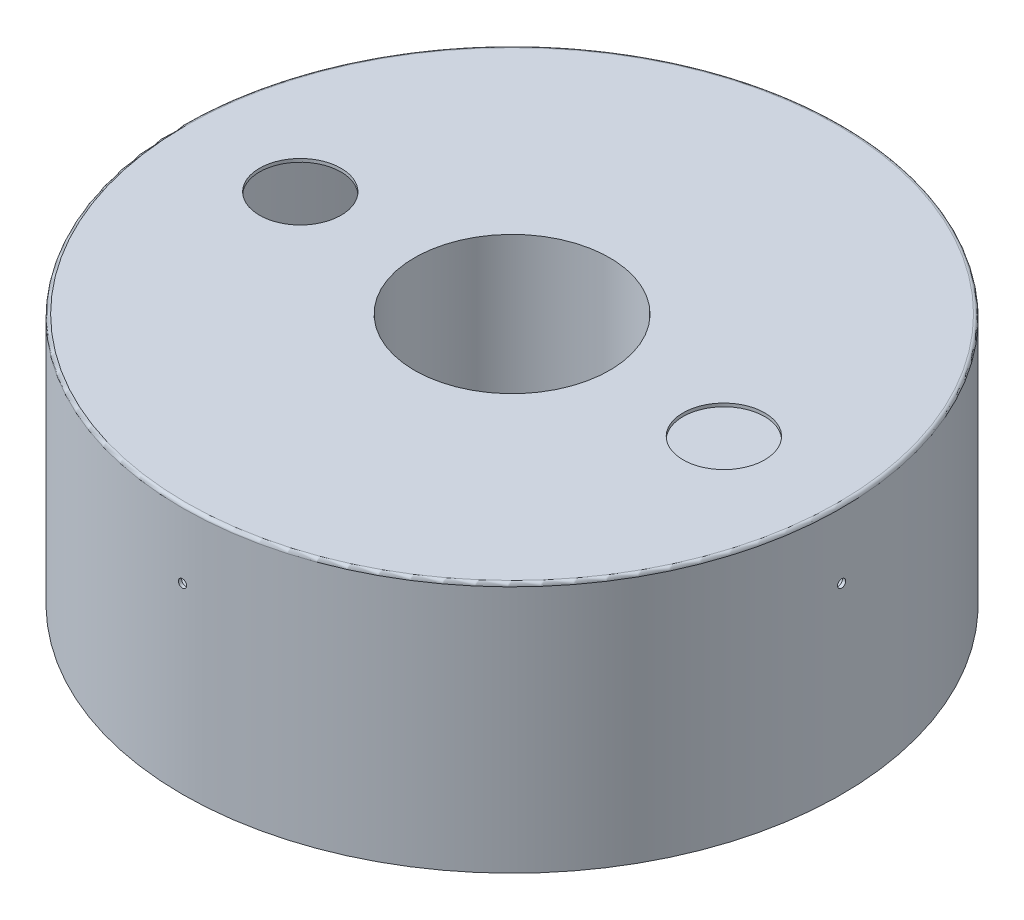
SolidWorks part; units mm, degrees
material "2014 Alloy"
ref_plane "Front Plane" through (0, 0, 0) normal (0, 0, 1) x (1, 0, 0)
ref_plane "Top Plane" through (0, 0, 0) normal (0, 1, 0) x (1, 0, 0)
ref_plane "Right Plane" through (0, 0, 0) normal (1, 0, 0) x (0, 0, -1)
sketch "Sketch9" plane through (0, 0, 0) normal (0, 1, 0) x (1, 0, 0)
  circle A0 centre (0, 0) radius 2000
extrude "Boss-Extrude5" add sketch "Sketch9" along normal blind 1500
sketch "Sketch10" plane through (0, 1500, 0) normal (0, 1, 0) x (1, 0, 0)
  circle A0 centre (0, 0) radius 598.217
extrude "Cut-Extrude3" cut sketch "Sketch10" against normal blind 1500
shell "Shell6" thickness 20 removed face at (0, 0, 598.217) outward yes
sketch "Sketch11" plane through (0, 1520, 0) normal (0, 1, 0) x (1, 0, 0)
  circle A0 centre (0, 0) radius 598.217
extrude "Boss-Extrude6" add sketch "Sketch11" against normal through all
sketch "Sketch13" plane through (0, 1520, 0) normal (0, 1, 0) x (1, 0, 0)
  circle A0 centre (0, 0) radius 618.217
extrude "Boss-Extrude7" add sketch "Sketch13" against normal through all
sketch "Sketch14" plane through (0, 1520, 0) normal (0, 1, 0) x (1, 0, 0)
  circle A0 centre (0, 0) radius 598.217
extrude "Cut-Extrude5" cut sketch "Sketch14" against normal through all
fillet "Fillet2" radius 20 1 edges at (0, 1520, 2020)
sketch "Sketch16" plane through (0, 1520, 0) normal (0, 1, 0) x (1, 0, 0)
  circle A0 centre (-1298.217, 0) radius 250
  circle A1 centre (1298.217, 0) radius 250
  dimension "D1" = 2
extrude "Cut-Extrude6" cut sketch "Sketch16" against normal blind 547 and the other way through all
sketch "Sketch19" plane through (0, 0, 0) normal (0, 0, 1) x (1, 0, 0)
  circle A0 centre (0, 1100) radius 24.963
extrude "Cut-Extrude11" cut sketch "Sketch19" along normal blind 300 and the other way blind 100 from offset 1800
pattern_circular "CirPattern1" count 4 every 90 about axis through (0, 1520, 0) along (0, 1, 0) of "Cut-Extrude11"
